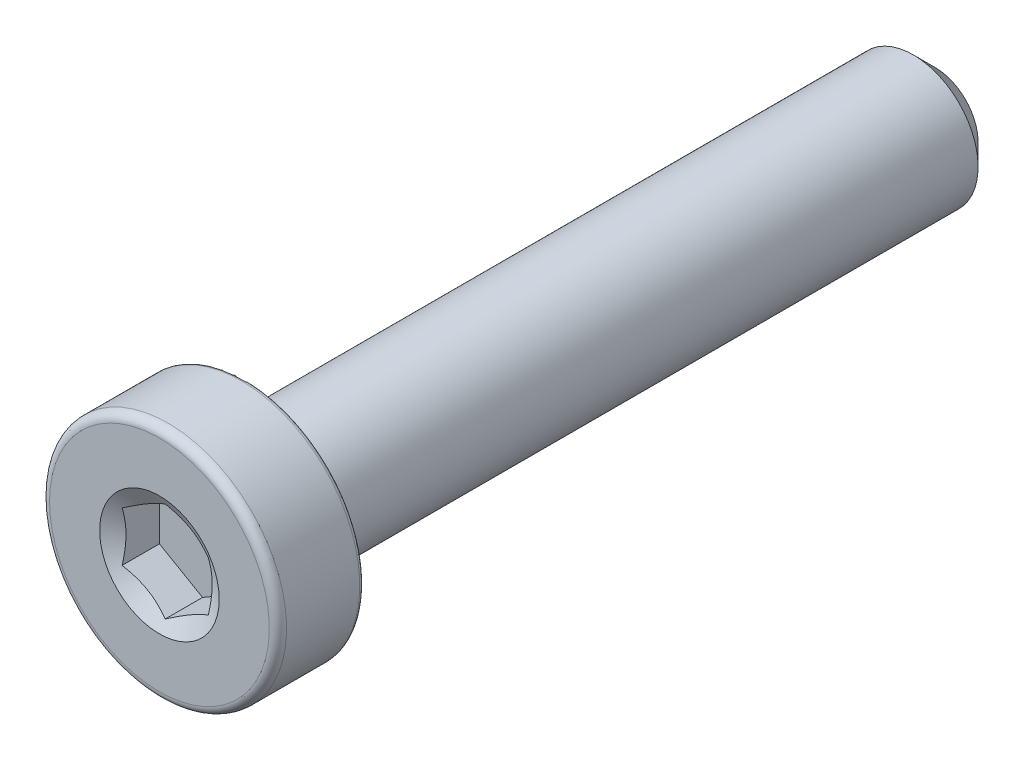
SolidWorks part; units mm, degrees
ref_plane "Front Plane" through (0, 0, 0) normal (0, 0, 1) x (1, 0, 0)
ref_plane "Top Plane" through (0, 0, 0) normal (0, 1, 0) x (1, 0, 0)
ref_plane "Right Plane" through (0, 0, 0) normal (1, 0, 0) x (0, 0, -1)
sketch "Sketch1" plane through (0, 0, 0) normal (1, 0, 0) x (0, 0, -1)
  line L0 (9, 0) -> (-9, 0) construction
  line L1 (-7, 2.75) -> (-7, -2.75) construction
  line L2 (9, 1.5) -> (9, -1.5) construction
  line L3 (8.9687, 1.5541) -> (9.2187, 1.1211) construction
  line L4 (9.1875, 1.1752) -> (9.25, 1.1752) construction
  line L5 (9.2187, 1.1211) -> (9.4687, 1.5541) construction
  line L6 (9.4687, 1.5541) -> (8.9687, 1.5541) construction
  line L7 (9.2187, 1.1752) -> (9.2187, 1.1211) construction
  line L8 (9.2187, 1.5541) -> (9.2187, 1.5) construction
  line L9 (9.4375, 1.5) -> (9, 1.5) construction
  line L10 (-9, -2.75) -> (-9, 2.75) construction
  point P4 (-7, 0)
  point P6 (-7, 1)
  point P7 (7.75, -1.5)
  point P20 (9.2187, 1.5271)
  point P23 (-9, 0)
  point P24 (-7, 2.75)
  point P25 (-9, 2.75)
  point P26 (-9, -2.75)
  point P27 (-7, -2.75)
  point P28 (9, -1.5)
  point P29 (9, 1.5)
  dimension "Head Height" = 2
  dimension "Head Diameter" = 5.5
  dimension "Drive Size" = 2
  dimension "Length" = 16
  dimension "Thread Size" = 3
  dimension "Thread Pitch" = 0.5
  dimension "Pitch/8" = 0.0625
  dimension "Thread Note" = 1.25
sketch "Sketch2" plane through (0, 0, 0) normal (1, 0, 0) x (0, 0, -1)
  line L0 (9, 0) -> (9, 1)
  line L1 (9, 1.5) -> (9, -1.5) construction
  line L2 (9, 1) -> (8.5, 1.5)
  line L3 (8.5, 1.5) -> (-7, 1.5)
  line L4 (-7, 1.5) -> (-7, 2.65)
  line L5 (-7.1, 2.75) -> (-8.8, 2.75)
  line L6 (-9, 2.55) -> (-9, 0)
  line L7 (9, 0) -> (-9, 0) construction
  line L8 (-9, 0) -> (9, 0)
  arc A0 (-7, 2.65) -> (-7.1, 2.75) centre (-7.1, 2.65) ccw
  arc A1 (-8.8, 2.75) -> (-9, 2.55) centre (-8.8, 2.55) ccw
  point P19 (-7, 2.75)
  dimension "D4" = 0.2
  dimension "D1" = 0.5
  dimension "D2" = 45
revolve "Revolve1" add sketch "Sketch2" angle 360 about L0
sketch "Sketch3" plane through (0, 0, 0) normal (0, 0, 1) x (1, 0, 0)
  line L0 (-1, -0.5774) -> (1, -0.5774) construction
  line L1 (-1, 0.5774) -> (-1, -0.5774)
  line L2 (-1, -0.5774) -> (0, -1.1547)
  line L3 (0, -1.1547) -> (1, -0.5774)
  line L4 (1, -0.5774) -> (1, 0.5774)
  line L5 (1, 0.5774) -> (0, 1.1547)
  line L6 (0, 1.1547) -> (-1, 0.5774)
  line L7 (-2.75, 0) -> (2.75, 0) construction
  circle A0 centre (0, 0) radius 1 construction
  circle A1 centre (0, 0) radius 2.75 construction
  point P12 (-1, -0.5774)
  point P14 (1, -0.5774)
  point P17 (-2.75, 0)
  point P18 (2.75, 0)
extrude "Cut-Extrude1" cut sketch "Sketch3" against normal blind 1 from vertex starting at point (0, 0, 9)
sketch "Sketch4" plane through (0, 0, 9) normal (0, 0, 1) x (1, 0, 0)
  line L0 (0, 1.1547) -> (0, 1.6198) construction
  line L1 (0, 1.6198) -> (0, 2.0849) construction
  line L2 (0, 2.0849) -> (0, 2.55) construction
  circle A0 centre (0, 0) radius 1.3873
  point P12 (0, 1.3873)
extrude "Cut-Extrude2" cut sketch "Sketch4" against normal through all draft 60
split "Split1" [suppressed] bodies to split 106 112
sketch "Sketch5" [suppressed] plane through (0, 0, 0) normal (1, 0, 0) x (0, 0, -1)
  line L0 (9.1875, 1.1752) -> (9.25, 1.1752)
  line L1 (9.25, 1.1752) -> (9.4531, 1.5271)
  line L2 (9.4531, 1.5271) -> (8.9844, 1.5271)
  line L3 (8.9844, 1.5271) -> (9.1875, 1.1752)
  line L4 (8.9687, 1.5541) -> (9.2187, 1.1211) construction
sketch "Sketch6" [suppressed] plane through (0, 0, -9) normal (0, 0, -1) x (-1, 0, 0)
  circle A0 centre (0, 0) radius 1.5
curve "Helix/Spiral1" [suppressed] pitch 0.5 height 16.5 turns 33
sweep "Cut-Sweep1" [suppressed] cut profiles "Sketch5" path "Helix/Spiral1"
sketch "Sketch7" [suppressed] plane through (0, 0, 7) normal (0, 0, -1) x (-1, 0, 0)
  circle A0 centre (0, 0) radius 1.5508
  circle A1 centre (0, 0) radius 1.5 construction
  dimension "D1" = 0.0508
extrude "Boss-Extrude1" [suppressed] add sketch "Sketch7" along normal blind 1.5 draft 20 and the other way blind 0.2
equation "\"Pitch/8@Sketch1\" = \"Thread Pitch@Sketch1\" / 8"
equation "\"Thread Note@Sketch1\" = \"Thread Pitch@Sketch1\" * 2.5"
equation "\"D1@Sketch2\" = \"Thread Pitch@Sketch1\""
equation "\"D3@Sketch2\"=\"Head Height@Sketch1\"*.05"
equation "\"D1@Cut-Extrude1\" = \"Head Height@Sketch1\" * .5"
equation "\"D3@Helix/Spiral1\" = \"Length@Sketch1\" + \"Thread Pitch@Sketch1\""
equation "\"D4@Helix/Spiral1\" = \"Thread Pitch@Sketch1\""
equation "\"D2@Boss-Extrude1\" = \"Head Height@Sketch1\" * .1"
equation "\"D1\"= \"Thread Size@Sketch1\" * .4"
equation "\"D1@Boss-Extrude1\" = \"Thread Pitch@Sketch1\" * 3"
equation "\"D4@Sketch2\"=\"D3@Sketch2\"*2"
